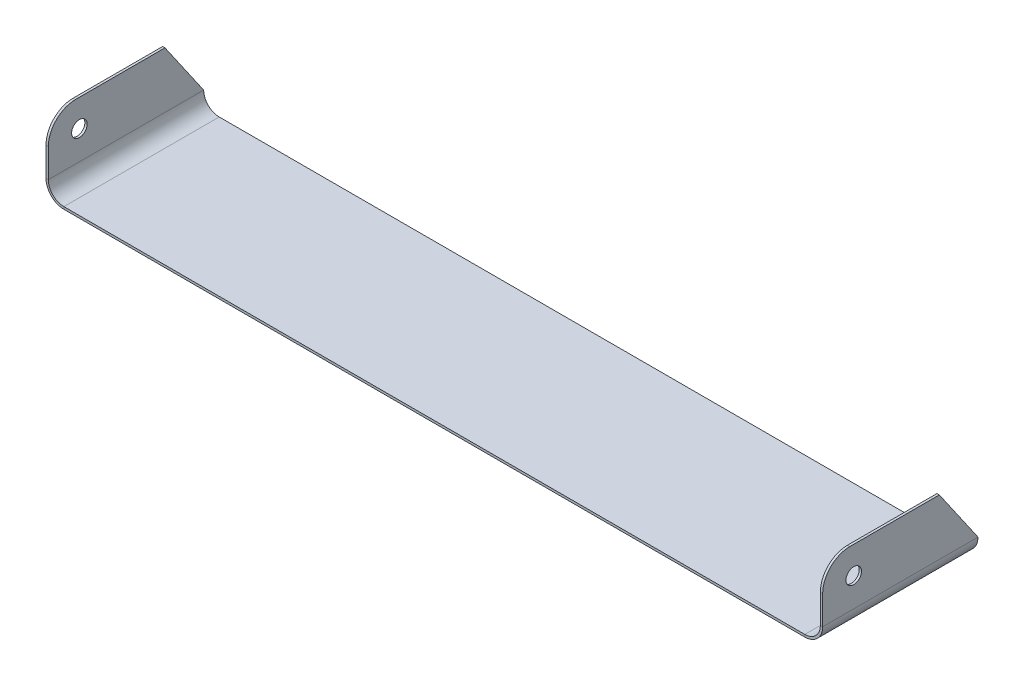
SolidWorks part; units mm, degrees
note: The reader was unsure of these and kept them because the rebuilt part matched: flange length of "Edge-Flange1", "Edge-Flange2".
ref_plane "Front Plane" through (0, 0, 0) normal (0, 0, 1) x (1, 0, 0)
ref_plane "Top Plane" through (0, 0, 0) normal (0, 1, 0) x (1, 0, 0)
ref_plane "Right Plane" through (0, 0, 0) normal (1, 0, 0) x (0, 0, -1)
sketch "Sketch1" plane through (0, 0, 0) normal (0, 1, 0) x (1, 0, 0)
  line L1 (-500, 100) -> (500, 100)
  line L2 (-500, 100) -> (-500, -100)
  line L3 (-500, -100) -> (500, -100)
  line L4 (500, 100) -> (500, -100)
  line L5 (-500, 100) -> (500, -100) construction
  line L6 (-500, -100) -> (500, 100) construction
  point P0 (0, 0)
base flange "Base-Flange1" sketch "Sketch1" thickness 3 reverse thickness direction no parameters "D1"=1
edge flange "Edge-Flange1" sketch "Sketch8" flange angle 90 flange length 95 flange position material inside bend radius 20 thickness 3 relief obround parameters "D6"=10
sketch "Sketch8" plane through (-500, 0, 0) normal (-1, 0, 0) x (0, 0, 1)
  line L0 (-100, 0) -> (100, 0) construction
  line L1 (-100, 0) -> (100, 0)
  line L2 (-100, 0) -> (-100, 92)
  line L3 (-100, 92) -> (65, 92)
  line L4 (100, 57) -> (100, 0)
  arc A0 (100, 57) -> (65, 92) centre (65, 57) ccw
  dimension "D1" = 35
bend "EdgeBend1" bend radius 20 bend angle 90 parameters "D5"=1
edge flange "Edge-Flange2" sketch "Sketch11" flange angle 90 flange length 95 flange position material inside bend radius 20 thickness 3 relief obround parameters "D6"=10
sketch "Sketch11" plane through (500, 0, 0) normal (1, 0, 0) x (0, 0, -1)
  line L0 (-100, 0) -> (100, 0) construction
  line L1 (-100, 0) -> (100, 0)
  line L2 (-100, 0) -> (-100, 57)
  line L3 (-65, 92) -> (100, 92)
  line L4 (100, 92) -> (100, 0)
  arc A0 (-65, 92) -> (-100, 57) centre (-65, 57) ccw
  dimension "D1" = 35
bend "EdgeBend2" bend radius 20 bend angle 90 parameters "D5"=2
sketch "Sketch13" plane through (-500, 0, 0) normal (-1, 0, 0) x (0, 0, 1)
  line L3 (-100, 20) -> (-50, 92.2451)
  line L4 (-50, 92.2451) -> (-100, 92)
  line L5 (-100, 92) -> (-100, 20)
  line L6 (100, -3) -> (-100, -3) construction
  line L7 (100, 20) -> (100, 57) construction
  circle A0 centre (60, 57) radius 10
  dimension "D2" = 60
  dimension "D3" = 40
extrude "Cut-Extrude1" cut sketch "Sketch13" against normal through all contours L3 L4 L5 | A0 normal cut yes
sketch "Bend-Lines1" [suppressed] plane through (0, 0, 0) normal (0, 1, 0) x (1, 0, 0)
sketch "Bounding-Box1" [suppressed] plane through (0, 0, 0) normal (0, 1, 0) x (1, 0, 0)
sheet metal parameters "Sheet-Metal1" thickness 3 parameters "D1"=1
flat pattern "Flat-Pattern1" [suppressed]
sketch "Bend-Lines2" plane through (0, 0, 0) normal (0, 1, 0) x (1, 0, 0)
sketch3d "Bounding-Box2" [suppressed]
  line L0 (-500, -100, 0) -> (500, -100, 0) construction
  line L1 (-500, 100, 0) -> (500, 100, 0) construction
  line L2 (-500, -100, 0) -> (-500, 100, 0) construction
  line L3 (500, -100, 0) -> (500, 100, 0) construction
sheet metal parameters "Sheet-Metal2" thickness 3 parameters "D1"=1
flat pattern "Flat-Pattern1"
sketch "Bend-Lines2" plane through (0, 0, 0) normal (0, 1, 0) x (1, 0, 0)
  line L0 (-497.9635, 100) -> (-497.9635, -100) construction
  line L1 (-497.9635, 100) -> (-497.9635, -100) construction
sketch3d "Bounding-Box2" [suppressed]
  line L0 (500, -100, 0) -> (-590.927, -100, 0) construction
  line L1 (500, 100, 0) -> (-590.927, 100, 0) construction
  line L2 (500, -100, 0) -> (500, 100, 0) construction
  line L3 (-590.927, -100, 0) -> (-590.927, 100, 0) construction
bend of the flat pattern "Flatten-<EdgeBend1>1"
sheet metal parameters "Sheet-Metal3" thickness 3 parameters "D1"=1
flat pattern "Flat-Pattern1"
sketch "Bend-Lines2" plane through (0, 0, 0) normal (0, 1, 0) x (1, 0, 0)
  line L0 (-493.8861, 100) -> (-493.8861, -100) construction
  line L1 (-493.8861, 100) -> (-493.8861, -100) construction
  line L2 (493.8861, -100) -> (493.8861, 100) construction
  line L3 (493.8861, -100) -> (493.8861, 100) construction
sketch3d "Bounding-Box2" [suppressed]
  line L0 (-582.7721, -100, 0) -> (582.7721, -100, 0) construction
  line L1 (-582.7721, 100, 0) -> (582.7721, 100, 0) construction
  line L2 (-582.7721, -100, 0) -> (-582.7721, 100, 0) construction
  line L3 (582.7721, -100, 0) -> (582.7721, 100, 0) construction
bend of the flat pattern "Flatten-<EdgeBend1>1"
bend of the flat pattern "Flatten-<EdgeBend2>1"
sheet metal parameters "Sheet-Metal4" thickness 3 parameters "D1"=1
flat pattern "Flat-Pattern1"
sketch "Bend-Lines2" plane through (0, 0, 0) normal (0, 1, 0) x (1, 0, 0)
  line L0 (-493.8861, 100) -> (-493.8861, -100) construction
  line L1 (-493.8861, 100) -> (-493.8861, -100) construction
  line L2 (493.8861, -100) -> (493.8861, 100) construction
  line L3 (493.8861, -100) -> (493.8861, 100) construction
sketch3d "Bounding-Box2" [suppressed]
  line L0 (-582.7721, -100, 0) -> (582.7721, -100, 0) construction
  line L1 (-582.7721, 100, 0) -> (582.7721, 100, 0) construction
  line L2 (-582.7721, -100, 0) -> (-582.7721, 100, 0) construction
  line L3 (582.7721, -100, 0) -> (582.7721, 100, 0) construction
bend of the flat pattern "Flatten-<EdgeBend1>1"
bend of the flat pattern "Flatten-<EdgeBend2>1"
